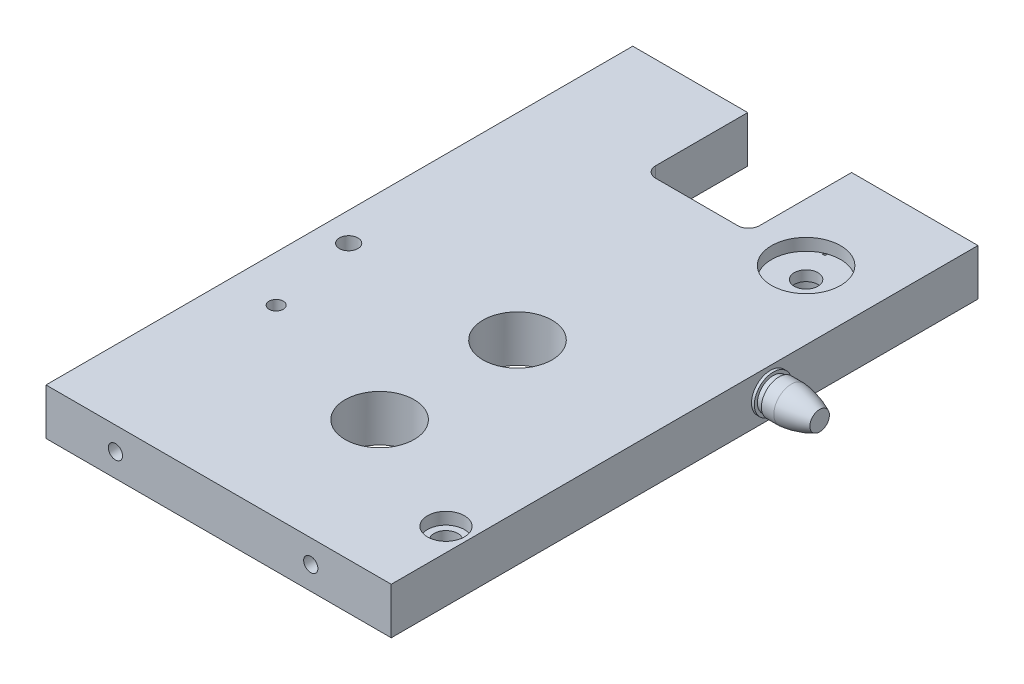
SolidWorks part; units mm, degrees
material "1060 Alloy"
ref_plane "Front Plane" through (0, 0, 0) normal (0, 0, 1) x (1, 0, 0)
ref_plane "Top Plane" through (0, 0, 0) normal (0, 1, 0) x (1, 0, 0)
ref_plane "Right Plane" through (0, 0, 0) normal (1, 0, 0) x (0, 0, -1)
sketch "Sketch1" plane through (0, 0, 0) normal (0, 0, 1) x (1, 0, 0)
  line L0 (-233.4699, -616.5) -> (-342.6239, -616.5) construction
  line L1 (-234.625, -610.1) -> (-329.875, -610.1)
  line L2 (-234.625, -610.1) -> (-234.625, -622.9)
  line L3 (-234.625, -622.9) -> (-329.875, -622.9)
  line L4 (-329.875, -610.1) -> (-329.875, -622.9)
  line L5 (-282.25, -610.1) -> (-282.25, -622.9) construction
  circle A0 centre (-307.5, -616.5) radius 3.1 construction
  circle A3 centre (-257, -616.5) radius 3.1 construction
  circle A4 centre (-244.2, -616.5) radius 2.395
  circle A5 centre (-257, -616.5) radius 3.1
  circle A6 centre (-307.5, -616.5) radius 3.1
  circle A7 centre (-320.5, -616.5) radius 2.395
  circle A10 centre (-320.5, -616.5) radius 3.425 construction
  circle A11 centre (-244.2, -616.5) radius 3.425 construction
  dimension "D3" = 4.79
  dimension "D1" = 12.8
  dimension "D2" = 95.25
extrude "Boss-Extrude1" add sketch "Sketch1" along normal blind 161.88 contours L2 L3 L4 L1
extrude "Cut-Extrude1" cut sketch "Sketch1<3>" along normal blind 20.2 contours A6 | A5 region at (-257, -616.5, 0) region at (-307.5, -616.5, 0)
sketch "Sketch1<3>" plane through (0, 0, 0) normal (0, 0, 1) x (1, 0, 0) same geometry as "Sketch1"
extrude "Cut-Extrude2" cut sketch "Sketch1<4>" along normal blind 21.5 contours A4 | A7 region at (-244.2, -616.5, 0) region at (-320.5, -616.5, 0)
sketch "Sketch1<4>" plane through (0, 0, 0) normal (0, 0, 1) x (1, 0, 0) same geometry as "Sketch1"
sketch "Sketch2" plane through (0, -610.1, 0) normal (0, 1, 0) x (1, 0, 0)
  line L0 (-234.625, 0) -> (-329.875, 0) construction
  line L1 (-269.505, 0) -> (-298.155, 0)
  line L2 (-269.505, 0) -> (-269.505, -25.4)
  line L3 (-272.505, -28.4) -> (-295.155, -28.4)
  line L4 (-298.155, 0) -> (-298.155, -25.4)
  line L5 (-272.505, -28.4) -> (-269.505, -28.4) construction
  line L6 (-269.505, -28.4) -> (-269.505, -25.4) construction
  line L7 (-295.155, -28.4) -> (-298.155, -28.4) construction
  line L8 (-298.155, -28.4) -> (-298.155, -25.4) construction
  line L9 (-275.57, -133.66) -> (-275.57, -161.88) construction
  line L10 (-234.625, -161.88) -> (-234.625, 0) construction
  line L11 (-329.875, -161.88) -> (-329.875, 0) construction
  line L12 (-234.625, -161.88) -> (-329.875, -161.88) construction
  line L13 (-266.045, -124.135) -> (-234.625, -124.135) construction
  line L14 (-266.045, -86.105) -> (-234.625, -86.105) construction
  line L15 (-275.57, -95.63) -> (-275.57, -161.88) construction
  circle A0 centre (-275.57, -124.135) radius 9.525
  circle A1 centre (-275.57, -86.105) radius 9.525
  arc A2 (-298.155, -25.4) -> (-295.155, -28.4) centre (-295.155, -25.4) ccw
  arc A3 (-272.505, -28.4) -> (-269.505, -25.4) centre (-272.505, -25.4) ccw
  dimension "D1" = 3
  dimension "D5" = 19.05
  dimension "D2" = 34.88
  dimension "D3" = 31.72
  dimension "D4" = 28.4
  dimension "D6" = 28.22
  dimension "D7" = 31.42
  dimension "D8" = 66.25
  dimension "D9" = 31.42
extrude "Cut-Extrude3" cut sketch "Sketch2" against normal up to next
sketch "Sketch3" plane through (0, -610.1, 0) normal (0, 1, 0) x (-1, 0, 0)
  line L0 (244.025, 28.505) -> (234.625, 28.505) construction
  line L1 (234.625, 161.88) -> (234.625, 0) construction
  line L2 (235.835, 140.49) -> (234.625, 140.49) construction
  line L3 (240.925, 145.58) -> (240.925, 161.88) construction
  line L4 (234.625, 161.88) -> (329.875, 161.88) construction
  line L5 (253.55, 38.03) -> (253.55, 161.88) construction
  line L6 (317.175, 111.08) -> (329.875, 111.08) construction
  line L7 (329.875, 161.88) -> (329.875, 0) construction
  line L8 (321.975, 86.28) -> (329.875, 86.28) construction
  line L9 (317.175, 111.08) -> (317.175, 161.88) construction
  line L10 (321.975, 86.28) -> (321.975, 161.88) construction
  circle A0 centre (240.925, 140.49) radius 3.265
  circle A1 centre (253.55, 28.505) radius 3.265
  circle A2 centre (240.925, 140.49) radius 5.09 construction
  circle A3 centre (253.55, 28.505) radius 9.525 construction
  circle A4 centre (317.175, 111.08) radius 1.96
  circle A5 centre (321.975, 86.28) radius 2.56
  dimension "D1" = 3.92
  dimension "D2" = 6.53
  dimension "D3" = 10.18
  dimension "D4" = 19.05
  dimension "D9" = 5.12
  dimension "D5" = 1.21
  dimension "D6" = 9.4
  dimension "D7" = 123.85
  dimension "D8" = 16.3
  dimension "D10" = 75.6
  dimension "D11" = 7.9
  dimension "D12" = 50.8
  dimension "D13" = 12.7
extrude "Cut-Extrude4" cut sketch "Sketch3" against normal up to next
sketch "Sketch4" plane through (0, -610.1, 0) normal (0, 1, 0) x (-1, 0, 0)
  circle A0 centre (253.55, 28.505) radius 9.525
  circle A1 centre (240.925, 140.49) radius 5.09
  circle A2 centre (253.55, 28.505) radius 9.525 construction
  circle A4 centre (240.925, 140.49) radius 5.09 construction
extrude "Cut-Extrude5" cut sketch "Sketch4" against normal blind 3.32
sketch "Sketch5" plane through (0, -622.9, 0) normal (0, -1, 0) x (1, 0, 0)
  circle A0 centre (-240.925, 140.49) radius 5.31
  circle A1 centre (-253.55, 28.505) radius 5.31
  circle A2 centre (-240.925, 140.49) radius 3.265 construction
  circle A3 centre (-253.55, 28.505) radius 3.265 construction
  dimension "D1" = 10.62
extrude "Cut-Extrude6" cut sketch "Sketch5" against normal blind 6.65
sketch "Sketch6" plane through (0, 0, 161.88) normal (0, 0, 1) x (1, 0, 0)
  circle A0 centre (-310.715, -616.48) radius 1.965
  circle A1 centre (-256.825, -616.48) radius 1.965
  circle A3 centre (-256.825, -616.48) radius 2.795 construction
  circle A4 centre (-310.715, -616.48) radius 2.795 construction
  dimension "D3" = 3.93
extrude "Cut-Extrude7" cut sketch "Sketch6" against normal blind 17.25
sketch "Sketch7" plane through (-329.875, 0, 0) normal (-1, 0, 0) x (0, 0, 1)
  line L0 (161.88, -616.5) -> (142.28, -616.5) construction
  line L1 (161.88, -610.1) -> (161.88, -622.9) construction
  circle A0 centre (142.28, -616.5) radius 1.97
  dimension "D1" = 3.94
  dimension "D2" = 19.6
extrude "Cut-Extrude8" cut sketch "Sketch7" against normal blind 15.87
ref_plane "Plane1" through (0, -616.5, 0) normal (0, 1, 0) x (-1, 0, 0)
sketch "Sketch8" plane through (0, -616.5, 0) normal (0, 1, 0) x (-1, 0, 0)
  line L0 (234.625, 57.29) -> (221.025, 57.29)
  line L1 (234.625, 57.29) -> (234.625, 52.09)
  line L2 (234.625, 161.88) -> (234.625, 0) construction
  line L3 (234.625, 57.29) -> (259.3185, 57.29) construction
  line L4 (234.625, 52.09) -> (233.835, 52.09)
  line L5 (233.835, 52.09) -> (233.835, 52.925)
  line L6 (233.835, 52.925) -> (232.295, 52.925)
  line L7 (232.295, 52.925) -> (232.2758, 52.475)
  line L8 (232.2758, 52.475) -> (228.8458, 52.475)
  line L9 (221.025, 57.29) -> (221.025, 54.59)
  line L10 (228.8458, 52.475) -> (228.8458, 75.3879) construction
  line L11 (228.8458, 75.3879) -> (230.8458, 75.3879) construction
  arc A0 (221.025, 54.59) -> (228.8458, 52.475) centre (230.8458, 75.3879) ccw
  dimension "D9" = 23
  dimension "D1" = 10.4
  dimension "D2" = 8.73
  dimension "D3" = 9.63
  dimension "D4" = 5.4
  dimension "D5" = 13.6
  dimension "D6" = 0.79
  dimension "D7" = 1.54
  dimension "D8" = 3.43
  dimension "D10" = 57.29
  dimension "D11" = 2
revolve "Revolve1" add sketch "Sketch8" angle 360 about L3
